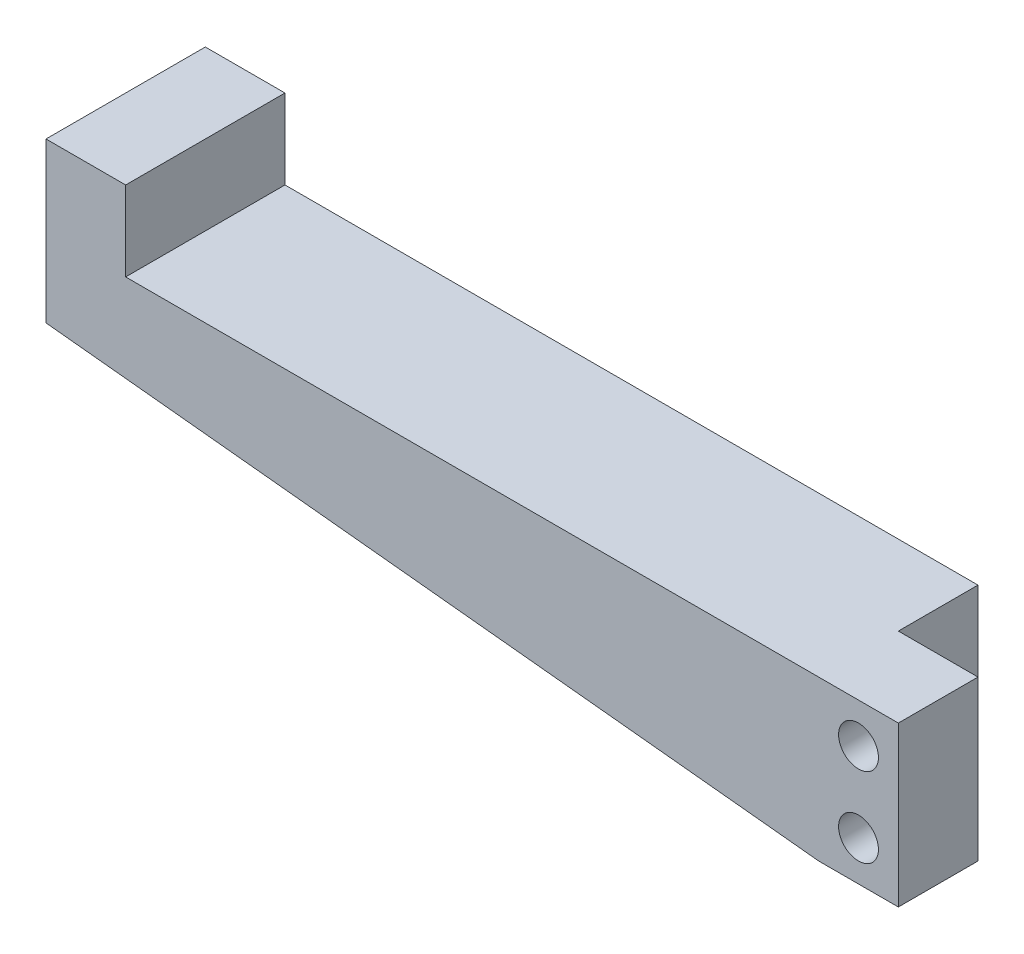
SolidWorks part; units mm, degrees
ref_plane "Plan de face" through (0, 0, 0) normal (0, 0, 1) x (1, 0, 0)
ref_plane "Plan de dessus" through (0, 0, 0) normal (0, 1, 0) x (1, 0, 0)
ref_plane "Plan de droite" through (0, 0, 0) normal (1, 0, 0) x (0, 0, -1)
sketch "Esquisse1" plane through (0, 0, 0) normal (0, 0, 1) x (1, 0, 0)
  line L0 (-102, 0) -> (-5, -10)
  line L1 (-5, -10) -> (5, -10)
  line L3 (-5, 10) -> (5, 10)
  line L4 (5, -10) -> (5, 10)
  line L5 (-5, -10) -> (5, 10) construction
  line L6 (-5, 10) -> (5, -10) construction
  line L7 (-5, 10) -> (-92, 10)
  line L10 (-102, 10) -> (-102, 0)
  line L12 (-102, 10) -> (-102, 20)
  line L13 (-102, 20) -> (-92, 20)
  line L14 (-92, 10) -> (-92, 20)
  circle A0 centre (0, 5) radius 2.5
  circle A1 centre (0, -5) radius 2.5
  point P0 (0, 0)
  dimension "D2" = 5
  dimension "D6" = 5
  dimension "D1" = 20
  dimension "D3" = 10
  dimension "D4" = 5
  dimension "D5" = 5
  dimension "D7" = 97
  dimension "D8" = 10
  dimension "D9" = 10
  dimension "D10" = 10
extrude "Boss.-Extru.1" add sketch "Esquisse1" along normal blind 20
sketch "Esquisse3" plane through (0, 0, 0) normal (0, 0, -1) x (-1, 0, 0)
  line L1 (-5, 10) -> (5, 10)
  line L2 (-5, 10) -> (-5, -10)
  line L3 (-5, -10) -> (5, -10)
  line L4 (5, 10) -> (5, -10)
extrude "Enlèv. mat.-Extru.2" cut sketch "Esquisse3" against normal blind 10
